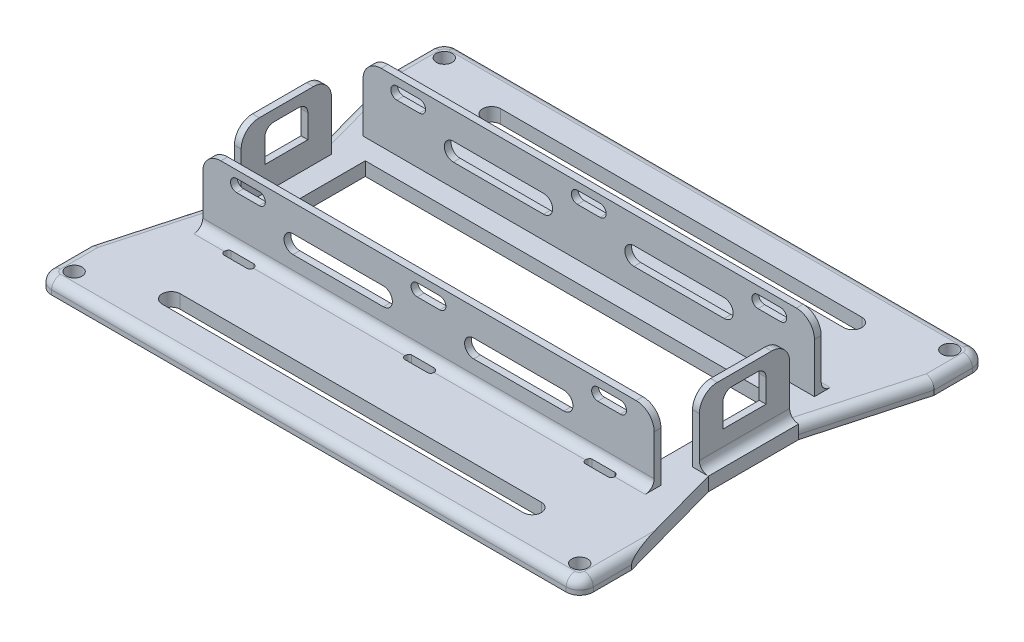
SolidWorks part; units mm, degrees
material "ABS"
ref_plane "Front Plane" through (0, 0, 0) normal (0, 0, 1) x (1, 0, 0)
ref_plane "Top Plane" through (0, 0, 0) normal (0, 1, 0) x (1, 0, 0)
ref_plane "Right Plane" through (0, 0, 0) normal (1, 0, 0) x (0, 0, -1)
sketch "Sketch1" plane through (0, 0, 0) normal (0, 1, 0) x (1, 0, 0)
  line L0 (0, 0) -> (0, 45) construction
  line L1 (-60, -45) -> (60, -45)
  line L2 (-60, -45) -> (-60, 45)
  line L3 (-60, 45) -> (60, 45)
  line L4 (60, -45) -> (60, 45)
  line L5 (-60, -45) -> (60, 45) construction
  line L6 (-60, 45) -> (60, -45) construction
  line L8 (-60, -13) -> (-60, 13)
  point P0 (0, 0)
  point P6 (-44.5, 0)
  point P12 (-60, 0)
  point P22 (0, 0)
  dimension "D2" = 26
  dimension "D3" = 15.5
  dimension "D13" = 120
  dimension "D14" = 90
extrude "Boss-Extrude1" add sketch "Sketch1" along normal blind 3 contours L4 L3 L2 L1 | L2 | L4 region at (0, 0, 0)
sketch "Sketch17" plane through (0, 3, 0) normal (0, 1, 0) x (1, 0, 0)
  line L0 (-60, -45) -> (-60, 45) construction
  line L7 (-60, 45) -> (60, 45) construction
  circle A3 centre (-56, 41) radius 1.75
  dimension "D1" = 3.5
  dimension "D2" = 4
  dimension "D3" = 4
extrude "Cut-Extrude11" cut sketch "Sketch17" against normal blind 4
mirror "Mirror13" about plane through (0, 0, 0) normal (1, 0, 0) of "Cut-Extrude11"
mirror "Mirror14" about plane through (0, 0, 0) normal (0, 0, 1) of "Mirror13"
sketch "Sketch19" plane through (0, 3, 0) normal (0, 1, 0) x (1, 0, 0)
  line L0 (-51.5, 10) -> (-50, 10)
  line L5 (-50, -17) -> (50, 17) construction
  line L6 (-50, 17) -> (50, -17) construction
  line L7 (-50, 17) -> (50, 17)
  line L8 (-50, 17) -> (-50, 18.5)
  line L9 (-50, 18.5) -> (50, 18.5)
  line L10 (50, 17) -> (50, 18.5)
  line L12 (50, 10) -> (50, -10)
  line L14 (51.5, 10) -> (51.5, -10)
  line L15 (-50, -17) -> (50, -17)
  line L16 (-50, -17) -> (-50, -18.5)
  line L17 (-50, -18.5) -> (50, -18.5)
  line L18 (50, -17) -> (50, -18.5)
  line L20 (-50, 10) -> (-50, -10)
  line L22 (-51.5, 10) -> (-51.5, -10)
  line L23 (50, 10) -> (51.5, 10)
  line L24 (-1.65, 0) -> (1.65, 0) construction
  line L25 (50, -10) -> (51.5, -10)
  line L26 (-51.5, -10) -> (-50, -10)
  point P0 (0, 0)
  dimension "D1" = 100
  dimension "D2" = 34
  dimension "D3" = 1.5
  dimension "D5" = 1.5
  dimension "D7" = 10
extrude "Boss-Extrude4" add sketch "Sketch19" along normal blind 15
sketch "Sketch20" plane through (0, 0, 18.5) normal (0, 0, 1) x (1, 0, 0)
  line L0 (-42.5, 15) -> (-37.5, 15) construction
  line L1 (-42.5, 16.3573) -> (-37.5, 16.3573)
  line L2 (-42.5, 13.6427) -> (-37.5, 13.6427)
  line L3 (-50, 18) -> (50, 18) construction
  line L4 (-50, 18) -> (-50, 3) construction
  line L5 (-2.5, 13.6427) -> (2.5, 13.6427)
  line L6 (-2.5, 16.3573) -> (2.5, 16.3573)
  line L7 (-2.5, 15) -> (2.5, 15) construction
  line L8 (37.5, 13.6427) -> (42.5, 13.6427)
  line L9 (37.5, 16.3573) -> (42.5, 16.3573)
  line L10 (37.5, 15) -> (42.5, 15) construction
  arc A0 (-42.5, 16.3573) -> (-42.5, 13.6427) centre (-42.5, 15) ccw
  arc A1 (-37.5, 13.6427) -> (-37.5, 16.3573) centre (-37.5, 15) ccw
  arc A2 (-2.5, 16.3573) -> (-2.5, 13.6427) centre (-2.5, 15) ccw
  arc A3 (2.5, 13.6427) -> (2.5, 16.3573) centre (2.5, 15) ccw
  arc A4 (37.5, 16.3573) -> (37.5, 13.6427) centre (37.5, 15) ccw
  arc A5 (42.5, 13.6427) -> (42.5, 16.3573) centre (42.5, 15) ccw
  point P2 (-40, 15)
  point P14 (0, 15)
  point P21 (40, 15)
  dimension "D1" = 3
  dimension "D2" = 10
  dimension "D3" = 5
  dimension "D4" = 3
extrude "Cut-Extrude12" cut sketch "Sketch20" against normal blind 38
sketch "Sketch21" plane through (0, 3, 0) normal (0, 1, 0) x (1, 0, 0)
  line L0 (-42.5, -20.5) -> (-37.5, -20.5) construction
  line L1 (-42.5, -19.7542) -> (-37.5, -19.7542)
  line L2 (-42.5, -21.2458) -> (-37.5, -21.2458)
  line L3 (-50, -18.5) -> (50, -18.5) construction
  line L4 (-2.5, -21.2458) -> (2.5, -21.2458)
  line L5 (-2.5, -19.7542) -> (2.5, -19.7542)
  line L6 (-2.5, -20.5) -> (2.5, -20.5) construction
  line L7 (37.5, -21.2458) -> (42.5, -21.2458)
  line L8 (37.5, -19.7542) -> (42.5, -19.7542)
  line L9 (37.5, -20.5) -> (42.5, -20.5) construction
  line L10 (-9.9, 0) -> (9.9, 0) construction
  line L11 (37.5, 20.5) -> (42.5, 20.5) construction
  line L12 (37.5, 19.7542) -> (42.5, 19.7542)
  line L13 (37.5, 21.2458) -> (42.5, 21.2458)
  line L14 (-2.5, 20.5) -> (2.5, 20.5) construction
  line L15 (-2.5, 19.7542) -> (2.5, 19.7542)
  line L16 (-2.5, 21.2458) -> (2.5, 21.2458)
  line L17 (-42.5, 20.5) -> (-37.5, 20.5) construction
  line L18 (-42.5, 19.7542) -> (-37.5, 19.7542)
  line L19 (-42.5, 21.2458) -> (-37.5, 21.2458)
  arc A0 (-42.5, -19.7542) -> (-42.5, -21.2458) centre (-42.5, -20.5) ccw
  arc A1 (-37.5, -21.2458) -> (-37.5, -19.7542) centre (-37.5, -20.5) ccw
  arc A2 (-2.5, -19.7542) -> (-2.5, -21.2458) centre (-2.5, -20.5) ccw
  arc A3 (2.5, -21.2458) -> (2.5, -19.7542) centre (2.5, -20.5) ccw
  arc A4 (37.5, -19.7542) -> (37.5, -21.2458) centre (37.5, -20.5) ccw
  arc A5 (42.5, -21.2458) -> (42.5, -19.7542) centre (42.5, -20.5) ccw
  arc A6 (37.5, 19.7542) -> (37.5, 21.2458) centre (37.5, 20.5) cw
  arc A7 (42.5, 21.2458) -> (42.5, 19.7542) centre (42.5, 20.5) cw
  arc A8 (-2.5, 19.7542) -> (-2.5, 21.2458) centre (-2.5, 20.5) cw
  arc A9 (2.5, 21.2458) -> (2.5, 19.7542) centre (2.5, 20.5) cw
  arc A10 (-42.5, 19.7542) -> (-42.5, 21.2458) centre (-42.5, 20.5) cw
  arc A11 (-37.5, 21.2458) -> (-37.5, 19.7542) centre (-37.5, 20.5) cw
  point P2 (-40, -20.5)
  point P14 (0, -20.5)
  point P21 (40, -20.5)
  point P28 (40, 20.5)
  point P35 (0, 20.5)
  point P42 (-40, 20.5)
  dimension "D1" = 10
  dimension "D2" = 5
  dimension "D3" = 2
  dimension "D4" = 3
extrude "Cut-Extrude13" cut sketch "Sketch21" against normal blind 38
fillet "Fillet1" radius 2 4 edges at (51.5, 3, 0) (0, 3, -18.5) (0, 3, 18.5) (-51.5, 3, 0)
sketch "Sketch22" plane through (51.5, 0, 0) normal (1, 0, 0) x (0, 0, -1)
  line L0 (-10, 18) -> (10, 18) construction
  line L1 (-4.7741, 8.4116) -> (4.7741, 8.4116)
  line L2 (-4.7741, 8.4116) -> (-4.7741, 13.5884)
  line L3 (-2.7741, 15.5884) -> (2.7741, 15.5884)
  line L4 (4.7741, 8.4116) -> (4.7741, 13.5884)
  line L5 (-4.7741, 8.4116) -> (4.7741, 15.5884) construction
  line L6 (-4.7741, 15.5884) -> (4.7741, 8.4116) construction
  arc A0 (2.7741, 15.5884) -> (4.7741, 13.5884) centre (2.7741, 13.5884) cw
  arc A1 (-4.7741, 13.5884) -> (-2.7741, 15.5884) centre (-2.7741, 13.5884) cw
  point P0 (0, 12)
  dimension "D2" = 2
  dimension "D1" = 6
extrude "Cut-Extrude14" cut sketch "Sketch22" against normal blind 104
sketch "Sketch23" plane through (0, 3, 0) normal (0, 1, 0) x (1, 0, 0)
  line L0 (40, -35.5) -> (-40, -35.5) construction
  line L1 (45, 12.5) -> (-45, 12.5)
  line L2 (45, 12.5) -> (45, -12.5)
  line L3 (45, -12.5) -> (-45, -12.5)
  line L4 (-45, 12.5) -> (-45, -12.5)
  line L5 (45, 12.5) -> (-45, -12.5) construction
  line L6 (45, -12.5) -> (-45, 12.5) construction
  line L7 (40, -37.5) -> (-40, -37.5)
  line L8 (40, -33.5) -> (-40, -33.5)
  line L9 (36.7542, -20.5) -> (3.2458, -20.5) construction
  line L10 (-9.9, 0) -> (9.9, 0) construction
  line L11 (40, 35.5) -> (-40, 35.5) construction
  line L12 (40, 37.5) -> (-40, 37.5)
  line L13 (40, 33.5) -> (-40, 33.5)
  line L14 (60, -33.5) -> (53.5, -10)
  line L15 (60, -45) -> (60, 45) construction
  line L16 (53.5, -10) -> (53.5, 10)
  line L17 (53.5, 10) -> (60, 33.5)
  line L18 (60, 33.5) -> (60, -33.5)
  line L19 (0, -9.9) -> (0, 9.9) construction
  line L20 (-53.5, 10) -> (-60, 33.5)
  line L21 (-53.5, -10) -> (-53.5, 10)
  line L22 (-60, -33.5) -> (-53.5, -10)
  line L23 (-60, 33.5) -> (-60, -33.5)
  arc A0 (40, -37.5) -> (40, -33.5) centre (40, -35.5) ccw
  arc A1 (-40, -33.5) -> (-40, -37.5) centre (-40, -35.5) ccw
  arc A2 (40, 37.5) -> (40, 33.5) centre (40, 35.5) cw
  arc A3 (-40, 33.5) -> (-40, 37.5) centre (-40, 35.5) cw
  point P0 (0, 0)
  point P8 (0, -35.5)
  point P21 (0, 35.5)
  dimension "D4" = 2
  dimension "D1" = 25
  dimension "D2" = 90
  dimension "D3" = 15
  dimension "D5" = 80
extrude "Cut-Extrude15" cut sketch "Sketch23" against normal blind 4
fillet "Fillet2" radius 3 4 edges at (60, 1.5, 45) (-60, 1.5, 45) (-60, 1.5, -45) (60, 1.5, -45)
fillet "Fillet3" radius 2 13 edges at (-60, 3, -37.75) (-59.1213, 3, -44.1213) (60, 3, -37.75) (59.1213, 3, -44.1213) (-60, 3, 37.75) (-59.1213, 3, 44.1213) (60, 3, 37.75) (59.1213, 3, 44.1213) (-56.75, 3, -21.75) (0, 3, -45) (56.75, 3, -21.75) (0, 3, 45) (-56.75, 3, 21.75)
fillet "Fillet4" radius 4 8 edges at (-50.75, 18, 10) (-50, 18, 17.75) (-50.75, 18, -10) (-50, 18, -17.75) (50, 18, -17.75) (50.75, 18, -10) (50.75, 18, 10) (50, 18, 17.75)
sketch "Sketch24" plane through (0, 0, 18.5) normal (0, 0, 1) x (1, 0, 0)
  line L0 (-30, 10) -> (-10, 10) construction
  line L1 (-30, 12) -> (-10, 12)
  line L2 (-30, 8) -> (-10, 8)
  line L3 (-50, 5) -> (50, 5) construction
  line L4 (0, -9.9) -> (0, 9.9) construction
  line L5 (30, 10) -> (10, 10) construction
  line L6 (30, 12) -> (10, 12)
  line L7 (30, 8) -> (10, 8)
  arc A0 (-30, 12) -> (-30, 8) centre (-30, 10) ccw
  arc A1 (-10, 8) -> (-10, 12) centre (-10, 10) ccw
  arc A2 (30, 12) -> (30, 8) centre (30, 10) cw
  arc A3 (10, 8) -> (10, 12) centre (10, 10) cw
  point P2 (-20, 10)
  point P14 (20, 10)
  dimension "D3" = 2
  dimension "D1" = 20
  dimension "D2" = 5
  dimension "D4" = 20
extrude "Cut-Extrude16" cut sketch "Sketch24" against normal blind 38 contours L6 A3 L7 A2 | L2 A1 L1 A0
